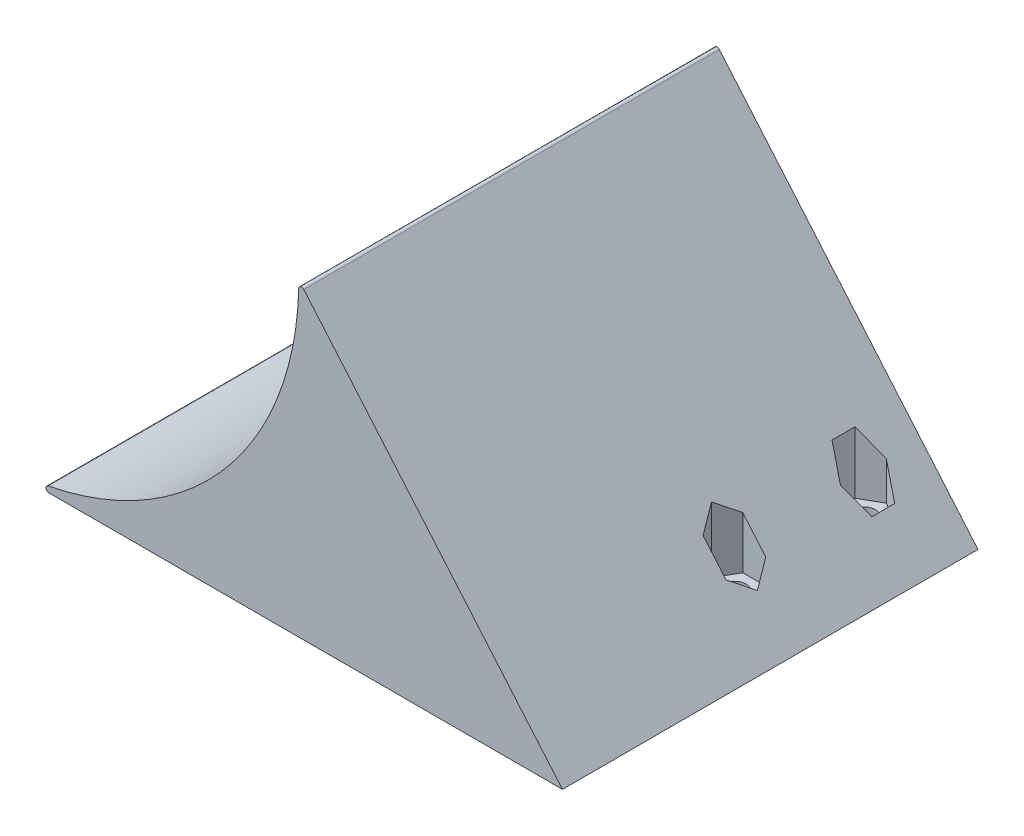
SolidWorks part; units mm, degrees
ref_plane "前视基准面" through (0, 0, 0) normal (0, 0, 1) x (1, 0, 0)
ref_plane "上视基准面" through (0, 0, 0) normal (0, 1, 0) x (1, 0, 0)
ref_plane "右视基准面" through (0, 0, 0) normal (1, 0, 0) x (0, 0, -1)
sketch "草图2" plane through (0, 0, 0) normal (0, 0, 1) x (1, 0, 0)
  circle A1 centre (0, 0) radius 33.5
  dimension "D3" = 67
sketch "草图3" plane through (0, 0, 0) normal (0, 0, 1) x (1, 0, 0)
  line L0 (0, 0) -> (0, -54) construction
  line L1 (0, -54) -> (100, -54) construction
  line L2 (100, -54) -> (0, -54)
  line L3 (54, 0) -> (100, -54)
  circle A1 centre (0, 0) radius 33.5 construction
  circle A2 centre (0, 0) radius 35.5
  arc A3 (0, -54) -> (54, 0) centre (0, 0) ccw
  dimension "D3" = 2
  dimension "D4" = 54
  dimension "D1" = 54
  dimension "D2" = 100
extrude "凸台-拉伸1" add sketch "草图3" along normal mid plane 145 contours A3 L2 A2 region at (60.1549, -37.9895, 0)
fillet "圆角1" radius 0.5 2 edges at (0, -54, 0) (54, 0, 0)
sketch "草图4" plane through (0, 0, 0) normal (0, 1, 0) x (1, 0, 0)
  line L1 (93.4641, -64.5) -> (93.4641, -60.5)
  line L2 (93.4641, -60.5) -> (90, -58.5)
  line L3 (90, -58.5) -> (86.5359, -60.5)
  line L4 (86.5359, -60.5) -> (86.5359, -64.5)
  line L5 (86.5359, -64.5) -> (90, -66.5)
  line L6 (90, -66.5) -> (93.4641, -64.5)
  line L7 (29.8923, -58.5) -> (26.4282, -60.5)
  line L8 (26.4282, -60.5) -> (26.4282, -64.5)
  line L9 (26.4282, -64.5) -> (29.8923, -66.5)
  line L10 (29.8923, -66.5) -> (33.3564, -64.5)
  line L11 (33.3564, -64.5) -> (33.3564, -60.5)
  line L12 (33.3564, -60.5) -> (29.8923, -58.5)
  line L14 (10.297, -72.5) -> (53.9837, -72.5) construction
  line L15 (90, -62.5) -> (90, 62.5) construction
  line L16 (9.8923, 72.5) -> (9.8923, -72.5) construction
  line L17 (0, 0) -> (131, 0) construction
  line L18 (-33.5, 0) -> (33.5, 0) construction
  line L19 (33.3564, 60.5) -> (29.8923, 58.5)
  line L20 (33.3564, 64.5) -> (33.3564, 60.5)
  line L21 (29.8923, 66.5) -> (33.3564, 64.5)
  line L22 (26.4282, 64.5) -> (29.8923, 66.5)
  line L23 (26.4282, 60.5) -> (26.4282, 64.5)
  line L24 (29.8923, 58.5) -> (26.4282, 60.5)
  line L25 (90, 66.5) -> (93.4641, 64.5)
  line L26 (86.5359, 64.5) -> (90, 66.5)
  line L27 (86.5359, 60.5) -> (86.5359, 64.5)
  line L28 (90, 58.5) -> (86.5359, 60.5)
  line L29 (93.4641, 60.5) -> (90, 58.5)
  line L30 (93.4641, 64.5) -> (93.4641, 60.5)
  line L31 (29.8923, -62.5) -> (90, -62.5) construction
  line L32 (92, -36.5359) -> (88, -36.5359)
  line L33 (88, -36.5359) -> (86, -40)
  line L34 (86, -40) -> (88, -43.4641)
  line L35 (88, -43.4641) -> (92, -43.4641)
  line L36 (92, -43.4641) -> (94, -40)
  line L37 (94, -40) -> (92, -36.5359)
  line L38 (94, 40) -> (92, 43.4641)
  line L39 (92, 43.4641) -> (88, 43.4641)
  line L40 (88, 43.4641) -> (86, 40)
  line L41 (86, 40) -> (88, 36.5359)
  line L42 (88, 36.5359) -> (92, 36.5359)
  line L43 (92, 36.5359) -> (94, 40)
  line L44 (90, -62.5) -> (93.4641, -114.585) construction
  line L45 (100, -72.5) -> (100, 72.5) construction
  circle A0 centre (90, -62.5) radius 3.4641 construction
  circle A1 centre (29.8923, -62.5) radius 3.4641 construction
  circle A2 centre (29.8923, 62.5) radius 3.4641 construction
  circle A3 centre (90, 62.5) radius 3.4641 construction
  circle A4 centre (90, -40) radius 3.4641 construction
  circle A5 centre (90, 40) radius 3.4641 construction
  dimension "D1" = 4
  dimension "D2" = 10
  dimension "D4" = 10
  dimension "D5" = 20
  dimension "D6" = 80
extrude "切除-拉伸1" cut sketch "草图4" against normal offset from surface (49 mm away) 5 up to face at (55.1962, -54, 0)
sketch "草图5" plane through (0, -49, 0) normal (0, 1, 0) x (1, 0, 0)
  line L0 (33.0636, -110) -> (26.1354, -110) construction
  line L1 (90, -62.5) -> (90, 62.5) construction
  line L3 (31.6244, -59.5) -> (28.1603, -65.5) construction
  line L6 (33.3564, -60.5) -> (29.8923, -58.5) construction
  line L7 (29.8923, -66.5) -> (26.4282, -64.5) construction
  line L8 (26.1354, -110) -> (33.0636, -110) construction
  line L10 (59.9462, 0) -> (0, 0) construction
  line L14 (59.9462, -110) -> (33.0636, -110) construction
  line L17 (59.9462, -110) -> (59.9462, 110) construction
  line L18 (26.4282, 62.5) -> (93.4641, 62.5) construction
  line L21 (-33.5, 0) -> (33.5, 0) construction
  line L22 (26.4282, 64.5) -> (26.4282, 60.5) construction
  line L25 (87, 38.2679) -> (93, 41.7321) construction
  line L27 (94, 40) -> (92, 43.4641) construction
  line L32 (86, 40) -> (88, 36.5359) construction
  circle A0 centre (29.8923, -62.5) radius 2.05
  circle A2 centre (29.8923, 62.5) radius 2.05
  circle A6 centre (90, 62.5) radius 2.05
  circle A7 centre (90, -62.5) radius 2.05
  circle A8 centre (90, 40) radius 2.05
  circle A9 centre (90, -40.0646) radius 2.05
  point P17 (59.9462, 62.5)
  point P49 (29.8923, -62.5)
  dimension "D1" = 4.1
extrude "切除-拉伸2" cut sketch "草图5" against normal blind 5 contours A0 | A8 | A2 | A7 | A9 | A6 region at (29.8923, -49, 62.5) region at (90, -49, -40)
sketch "草图6" plane through (0, 0, 0) normal (0, 0, 1) x (1, 0, 0)
  line L0 (100, -54) -> (10.3923, -54) construction
  circle A0 centre (51.8987, -54) radius 74.1946
extrude "切除-拉伸3" cut sketch "草图6" along normal through all
